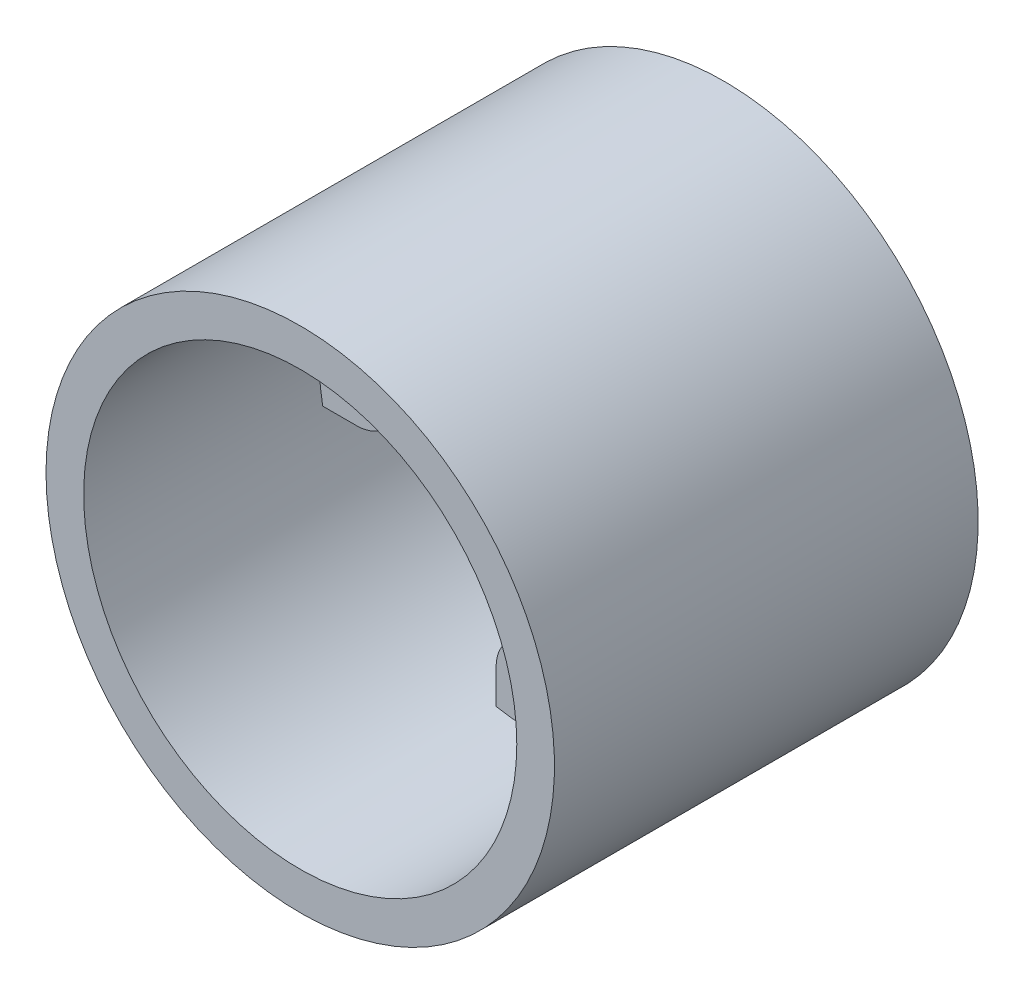
SolidWorks part; units mm, degrees
ref_plane "Front Plane" through (0, 0, 0) normal (0, 0, 1) x (1, 0, 0)
ref_plane "Top Plane" through (0, 0, 0) normal (0, 1, 0) x (1, 0, 0)
ref_plane "Right Plane" through (0, 0, 0) normal (1, 0, 0) x (0, 0, -1)
sketch "Sketch1" plane through (0, 0, 0) normal (0, 0, 1) x (1, 0, 0)
  line L0 (0, 0) -> (0, 19) construction
  line L1 (-4.2, 19) -> (-4.2, 22.6133)
  line L2 (4.2, 19) -> (4.2, 22.6133)
  line L3 (19, 4.2) -> (22.6133, 4.2)
  line L4 (19, -4.2) -> (22.6133, -4.2)
  line L5 (4.2, -19) -> (4.2, -22.6133)
  line L6 (-4.2, -19) -> (-4.2, -22.6133)
  line L7 (-19, -4.2) -> (-22.6133, -4.2)
  line L8 (-19, 4.2) -> (-22.6133, 4.2)
  circle A0 centre (0, 0) radius 23
  circle A1 centre (0, 19) radius 1.7
  arc A2 (-4.2, 19) -> (4.2, 19) centre (0, 19) ccw
  circle A3 centre (19, 0) radius 1.7
  arc A4 (19, 4.2) -> (19, -4.2) centre (19, 0) ccw
  circle A5 centre (0, -19) radius 1.7
  arc A6 (4.2, -19) -> (-4.2, -19) centre (0, -19) ccw
  circle A7 centre (-19, 0) radius 1.7
  arc A8 (-19, -4.2) -> (-19, 4.2) centre (-19, 0) ccw
  circle A9 centre (0, 0) radius 27
  point P30 (0, 0)
  dimension "D1" = 46
  dimension "D3" = 3.4
  dimension "D4" = 8.4
  dimension "D7" = 4
  dimension "D2" = 19
  dimension "D5" = 4
extrude "Boss-Extrude1" add sketch "Sketch1" along normal blind 45 contours A9 A0 region at (-26.2363, 0, 0)
extrude "Boss-Extrude2" add sketch "Sketch1<3>" along normal blind 20 contours L3 A4 L4 A0 A3 | L5 A6 L6 A0 A5 | L7 A8 L8 A0 A7 | L1 A2 L2 A0 A1 region at (-4.0826, 20.8066, 0) region at (-20.8066, 4.0826, 0) region at (22.7862, 2.0981, 0) region at (-4.0826, -20.8066, 0)
sketch "Sketch1<3>" plane through (0, 0, 0) normal (0, 0, 1) x (1, 0, 0) same geometry as "Sketch1"
